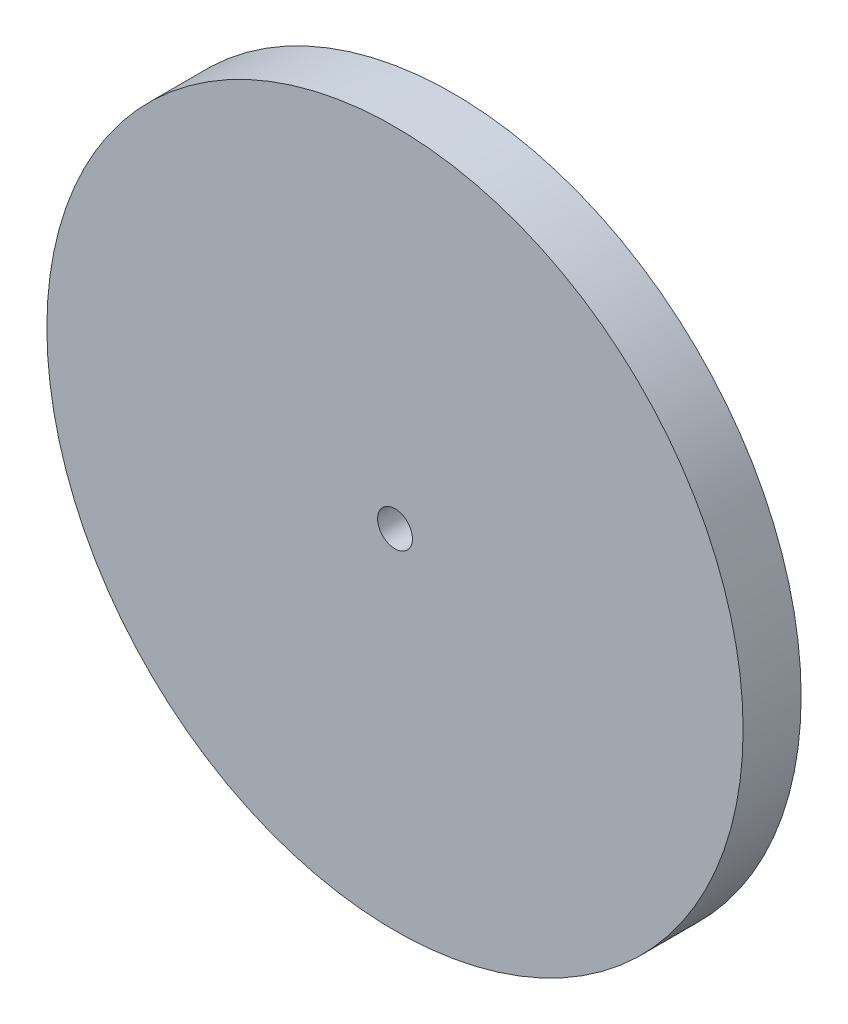
SolidWorks part; units mm, degrees
ref_plane "Front Plane" through (0, 0, 0) normal (0, 0, 1) x (1, 0, 0)
ref_plane "Top Plane" through (0, 0, 0) normal (0, 1, 0) x (1, 0, 0)
ref_plane "Right Plane" through (0, 0, 0) normal (1, 0, 0) x (0, 0, -1)
sketch "Sketch1" plane through (0, 0, 0) normal (0, 0, 1) x (1, 0, 0)
  circle A0 centre (0, 0) radius 30
  circle A1 centre (0, 0) radius 1.5
  dimension "D1" = 60
  dimension "D2" = 3
extrude "Boss-Extrude1" add sketch "Sketch1" along normal blind 5
